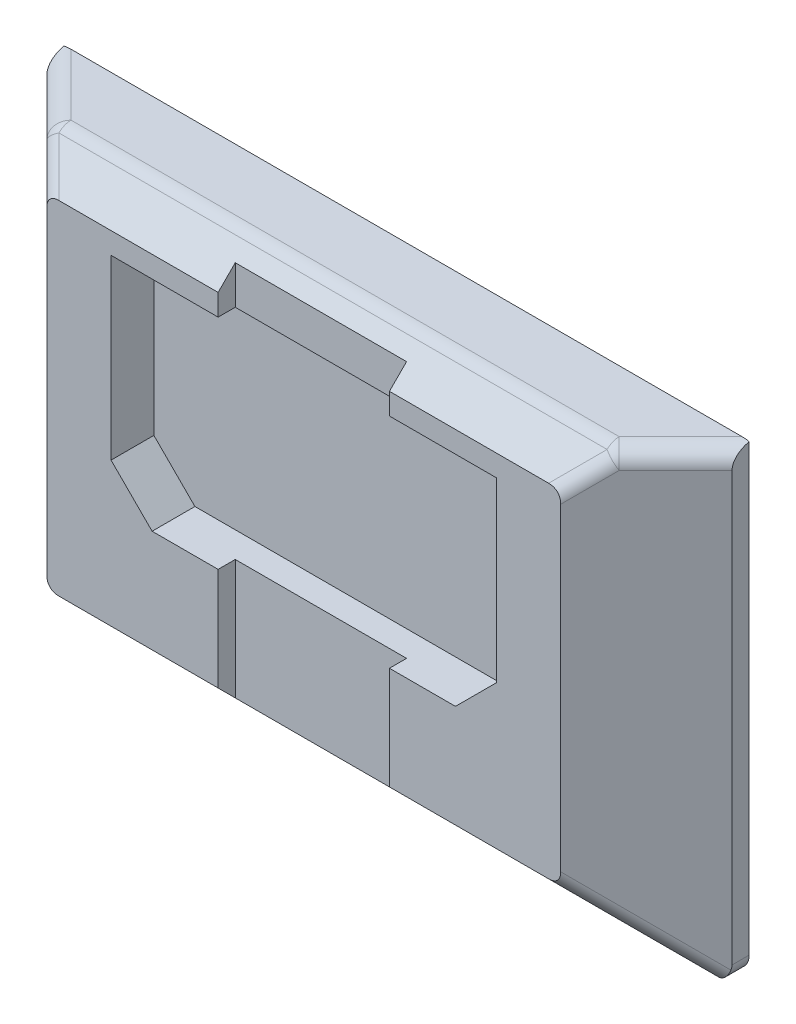
SolidWorks part; units mm, degrees
ref_plane "Front Plane" through (0, 0, 0) normal (0, 0, 1) x (1, 0, 0)
ref_plane "Top Plane" through (0, 0, 0) normal (0, 1, 0) x (1, 0, 0)
ref_plane "Right Plane" through (0, 0, 0) normal (1, 0, 0) x (0, 0, -1)
sketch "Sketch1" plane through (0, 0, 0) normal (0, 0, 1) x (1, 0, 0)
  line L1 (-40, -30) -> (40, -30)
  line L2 (-40, -30) -> (-40, 30)
  line L3 (-40, 30) -> (40, 30)
  line L4 (40, -30) -> (40, 30)
  line L5 (-40, -30) -> (40, 30) construction
  line L6 (-40, 30) -> (40, -30) construction
  point P0 (0, 0)
  dimension "D1" = 80
  dimension "D2" = 60
extrude "Boss-Extrude1" add sketch "Sketch1" along normal blind 12
chamfer "Chamfer1" distance 10 angle 45 4 edges at (-40, 0, 12) (0, 30, 12) (40, 0, 12) (0, -30, 12)
sketch "Sketch2" plane through (0, -30, 0) normal (0, -1, 0) x (1, 0, 0)
  line L0 (-30, 12) -> (30, 12) construction
  line L1 (-10, 12) -> (10, 12)
  line L2 (-10, 12) -> (-10, 10)
  line L3 (-10, 10) -> (10, 10)
  line L4 (10, 12) -> (10, 10)
  point P6 (0, 10)
  dimension "D1" = 20
  dimension "D2" = 2
extrude "Cut-Extrude1" cut sketch "Sketch2" against normal through all
sketch "Sketch3" plane through (40, 0, 0) normal (1, 0, 0) x (0, 0, -1)
  line L0 (-9, 15) -> (-4, 15) construction
  line L1 (-9, 16) -> (-4, 16)
  line L2 (-9, 14) -> (-4, 14)
  line L3 (-9, 11) -> (-4, 11) construction
  line L4 (-9, 12) -> (-4, 12)
  line L5 (-9, 10) -> (-4, 10)
  line L6 (-2, 30) -> (-2, -30) construction
  arc A0 (-9, 16) -> (-9, 14) centre (-9, 15) ccw
  arc A1 (-4, 14) -> (-4, 16) centre (-4, 15) ccw
  arc A2 (-9, 12) -> (-9, 10) centre (-9, 11) ccw
  arc A3 (-4, 10) -> (-4, 12) centre (-4, 11) ccw
  point P2 (-6.5, 15)
  point P9 (-6.5, 11)
  dimension "D3" = 1
  dimension "D4" = 1
  dimension "D1" = 5
  dimension "D2" = 5
  dimension "D5" = 4
  dimension "D6" = 15
  dimension "D7" = 2
  dimension "D8" = 2
extrude "Cut-Extrude2" cut sketch "Sketch3" against normal blind 8 from offset 72 offset against normal yes
fillet "Fillet1" radius 2 8 edges at (40, 30, 1) (35, 25, 7) (-35, 25, 7) (-40, 30, 1) (-35, -25, 7) (-40, -30, 1) (35, -25, 7) (40, -30, 1)
sketch "Sketch4" plane through (0, 0, 12) normal (0, 0, 1) x (1, 0, 0)
  line L0 (-22, 17) -> (-22, -3)
  line L1 (-22, -3) -> (-17.5, -7.5)
  line L2 (-17.5, -7.5) -> (17.5, -7.5)
  line L3 (17.5, -7.5) -> (22, -3)
  line L4 (22, -3) -> (22, 17)
  line L10 (-22, 17) -> (22, 17)
  line L11 (28.5858, 20) -> (10, 20) construction
  point P6 (0, -7.5)
  dimension "D1" = 3
  dimension "D2" = 20
  dimension "D3" = 35
  dimension "D4" = 44
  dimension "D5" = 7.5
  dimension "D6" = 4.5
  dimension "D7" = 4.5
  dimension "D9" = 4.5
extrude "Cut-Extrude3" cut sketch "Sketch4" against normal blind 5
sketch "Sketch5" plane through (-40, 0, 0) normal (-1, 0, 0) x (0, 0, 1)
  line L1 (0, 30) -> (10, 30)
  line L2 (0, 30) -> (0, 24)
  line L3 (0, 24) -> (10, 24)
  line L4 (10, 30) -> (10, 24)
  dimension "D1" = 10
  dimension "D2" = 6
extrude "Cut-Extrude4" cut sketch "Sketch5" against normal through all
fillet "Fillet2" radius 2 5 edges at (-37.7071, 24, 4.2929) (-34, 24, 7.6211) (37.7071, 24, 4.2929) (34, 24, 7.6211) (0, 24, 8)
sketch "Sketch6" plane through (0, 0, 12) normal (0, 0, 1) x (1, 0, 0)
  line L0 (22.5, 17.5) -> (-22.5, 17.5)
  line L1 (-22.5, 17.5) -> (-22.5, -3.2071)
  line L2 (-22.5, -3.2071) -> (-17.7071, -8)
  line L3 (-17.7071, -8) -> (17.7071, -8)
  line L4 (17.7071, -8) -> (22.5, -3.2071)
  line L5 (22.5, -3.2071) -> (22.5, 17.5)
  line L6 (22, 17) -> (-22, 17)
  line L7 (-22, 17) -> (-22, -3)
  line L8 (-22, -3) -> (-17.5, -7.5)
  line L9 (-17.5, -7.5) -> (17.5, -7.5)
  line L10 (17.5, -7.5) -> (22, -3)
  line L11 (22, -3) -> (22, 17)
  line L12 (22, 17) -> (-22, 17) construction
  line L13 (-22, 17) -> (-22, -3) construction
  line L14 (-22, -3) -> (-17.5, -7.5) construction
  line L15 (-17.5, -7.5) -> (17.5, -7.5) construction
  line L16 (17.5, -7.5) -> (22, -3) construction
  line L17 (22, -3) -> (22, 17) construction
  dimension "D1" = 0
  dimension "D2" = 0.5
extrude "Cut-Extrude5" cut sketch "Sketch6" against normal up to surface (5 mm away) up to face at (0, 2.1667, 7)
